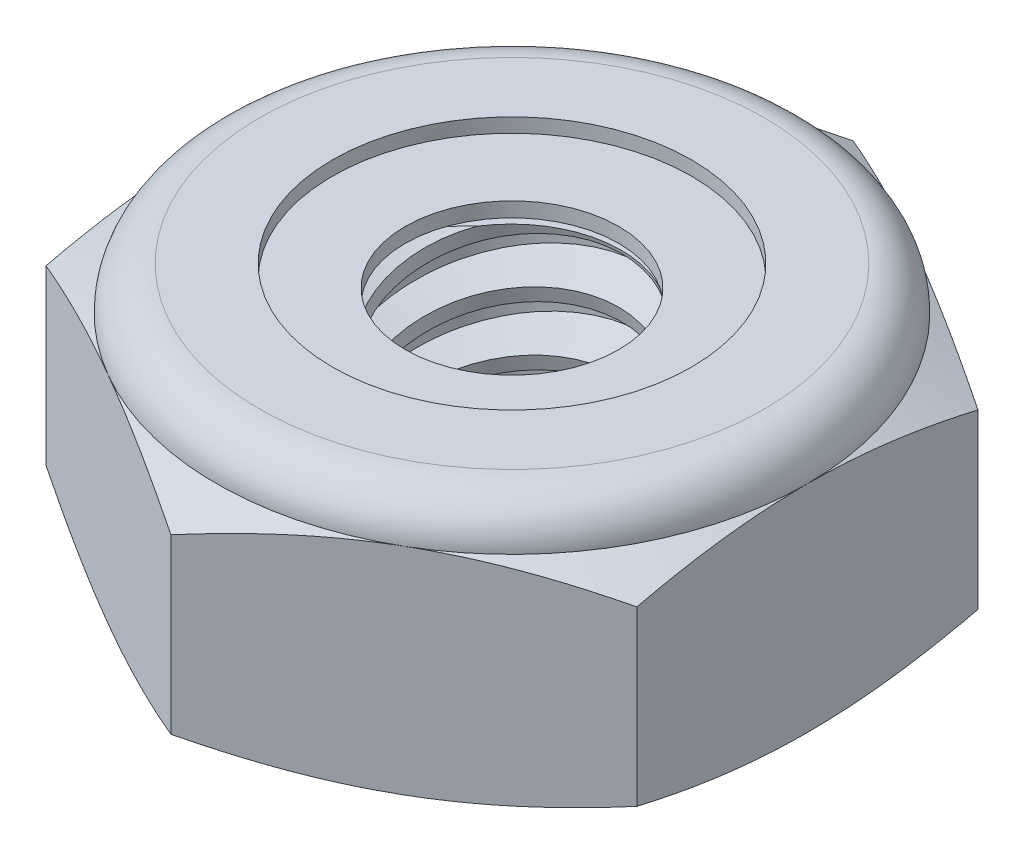
SolidWorks part; units mm, degrees
ref_plane "Front" through (0, 0, 0) normal (0, 0, 1) x (1, 0, 0)
ref_plane "Top" through (0, 0, 0) normal (0, 1, 0) x (1, 0, 0)
ref_plane "Right" through (0, 0, 0) normal (1, 0, 0) x (0, 0, -1)
sketch "Sketch1" plane through (0, 0, 0) normal (0, 1, 0) x (1, 0, 0)
  line L1 (0, 3.6662) -> (-3.175, 1.8331)
  line L2 (-3.175, 1.8331) -> (-3.175, -1.8331)
  line L3 (-3.175, -1.8331) -> (0, -3.6662)
  line L4 (0, -3.6662) -> (3.175, -1.8331)
  line L5 (3.175, -1.8331) -> (3.175, 1.8331)
  line L6 (3.175, 1.8331) -> (0, 3.6662)
  circle A0 centre (0, 0) radius 3.175 construction
  dimension "Hex Flats" = 6.35
extrude "Extrude1" add sketch "Sketch1" along normal blind 2.7781
sketch "Sketch2" plane through (0, 0, 0) normal (1, 0, 0) x (0, 0, -1)
  line L0 (-1.4224, 0) -> (-1.4224, 2.7781) construction
  line L1 (0, 0) -> (1.4224, 0)
  line L2 (0, 0) -> (0, 2.7781)
  line L3 (0, 2.7781) -> (1.4224, 2.7781)
  line L4 (1.4224, 0) -> (1.4224, 2.7781)
  line L5 (-1.8331, 2.7781) -> (1.8331, 2.7781) construction
  line L7 (0, -1.4224) -> (0, 0) construction
  dimension "Thread Dia" = 2.8448
revolve "Revolve1" add sketch "Sketch2" angle 360 about L7
sketch "Sketch3" plane through (0, 0, 0) normal (1, 0, 0) x (0, 0, -1)
  line L0 (1.4224, 2.7781) -> (-1.4224, 2.7781) construction
  line L1 (-1.4224, 2.7781) -> (-1.4224, 2.1431) construction
  line L2 (-1.4224, 2.1431) -> (1.4224, 2.7781) construction
  line L3 (1.4224, 2.7781) -> (1.4397, 2.7007) construction
  line L4 (1.4397, 2.7007) -> (1.5607, 2.1584)
  line L5 (1.5607, 2.1584) -> (1.1821, 2.2772)
  line L6 (1.1821, 2.2772) -> (1.1475, 2.4321)
  line L7 (1.1475, 2.4321) -> (1.4397, 2.7007)
  line L8 (1.1648, 2.3546) -> (1.5002, 2.4295) construction
  line L9 (1.4224, 2.7781) -> (1.4224, 2.4121) construction
  line L10 (1.4224, 2.4121) -> (-1.4224, 1.7771) construction
  line L11 (-1.4224, 1.7771) -> (-1.4224, 2.1431) construction
  line L12 (-0.1526, 2.7781) -> (0.1526, 1.4112) construction
  line L13 (-1.4224, 0) -> (-1.4224, 2.7781) construction
  line L14 (0, 2.7781) -> (1.4224, 2.7781) construction
  line L15 (1.4224, 0) -> (1.4224, 2.7781) construction
  point P13 (0, 2.0946)
  dimension "D1" = 0.0794
  dimension "D2" = 0.1588
  dimension "Thread Pitch" = 0.635
  dimension "D4" = 60
  dimension "D5" = 0.635
revolve "Cut-Revolve1" cut sketch "Sketch3" angle 360 about L12
pattern_linear "LPattern1" count 4 spacing 0.635 along (0, -1, 0) count 2 spacing 0.635 along (0, 1, 0) of "Cut-Revolve1"
sketch "Sketch4" plane through (0, 0, 0) normal (1, 0, 0) x (0, 0, -1)
  line L0 (0, 2.7781) -> (1.4224, 2.7781)
  line L1 (1.4224, 2.7781) -> (1.1475, 2.6499)
  line L2 (1.1475, 2.6499) -> (1.1475, 0.1282)
  line L3 (1.1475, 0.1282) -> (1.4224, 0)
  line L4 (1.4224, 0) -> (0, 0)
  line L5 (0, 0) -> (0, 2.7781)
  line L6 (1.4224, 0) -> (1.4224, 2.7781) construction
  line L7 (0, 2.7781) -> (1.4224, 2.7781) construction
  line L8 (0, 0) -> (1.4224, 0) construction
  line L9 (0, 0) -> (0, 2.7781) construction
  line L10 (0, 2.7781) -> (0, 3.0815) construction
  dimension "D1" = 25
revolve "Cut-Revolve2" cut sketch "Sketch4" angle 360 about L10
combine bodies "Combine1" operation type subtract main body 112 bodies to subtract 111
sketch "Sketch5" plane through (0, 0, 0) normal (1, 0, 0) x (0, 0, -1)
  line L0 (0, 0) -> (3.175, 0)
  line L1 (3.175, 0) -> (3.6662, 0.229)
  line L2 (3.6662, 0.229) -> (3.6662, 2.0861)
  line L3 (3.6662, 2.0861) -> (3.175, 2.3151)
  line L4 (2.712, 2.7781) -> (2.712, 4.0481)
  line L5 (2.712, 4.0481) -> (4.9362, 4.0481)
  line L6 (4.9362, 4.0481) -> (4.9362, -1.27)
  line L7 (4.9362, -1.27) -> (0, -1.27)
  line L8 (0, -1.27) -> (0, 0)
  line L9 (3.175, 2.3151) -> (3.175, 0) construction
  line L10 (0, 0) -> (1.4224, 0) construction
  line L13 (3.6662, 1.1576) -> (4.9362, 1.1576) construction
  line L14 (3.6662, 2.7781) -> (3.6662, 0) construction
  line L15 (0, 0) -> (0, 4.0481) construction
  line L20 (0, 4.0481) -> (2.712, 4.0481) construction
  line L22 (0, 2.7781) -> (1.4224, 2.7781) construction
  arc A0 (3.175, 2.3151) -> (2.712, 2.7781) centre (2.712, 2.3151) ccw
  dimension "D1" = 25
  dimension "D2" = 1.27
  dimension "D3" = 2.7781
  dimension "D4" = 0.463
revolve "Cut-Revolve3" cut sketch "Sketch5" angle 360 about L15
sketch "Sketch6" plane through (0, 0, 0) normal (1, 0, 0) x (0, 0, -1)
  line L0 (0, 2.3151) -> (3.0226, 2.3151)
  line L1 (2.712, 2.6257) -> (1.9297, 2.6257)
  line L2 (0, 4.0481) -> (0, 2.3151)
  line L3 (1.9297, 4.0481) -> (0, 4.0481)
  line L4 (0, 4.0481) -> (2.712, 4.0481) construction
  line L5 (0, 0) -> (0, 4.0481) construction
  line L6 (0, 4.0481) -> (0, 44.323) construction
  line L7 (1.9297, 2.6257) -> (1.9297, 4.0481)
  line L8 (2.712, 2.7781) -> (2.712, 2.6257) construction
  line L9 (1.9297, 2.6257) -> (1.1475, 2.6257) construction
  line L10 (1.1475, 2.6257) -> (1.1475, 2.6499) construction
  arc A0 (3.0226, 2.3151) -> (2.712, 2.6257) centre (2.712, 2.3151) ccw
  arc A1 (3.175, 2.3151) -> (2.712, 2.7781) centre (2.712, 2.3151) ccw construction
  dimension "D1" = 0.1524
revolve "Cut-Revolve4" cut sketch "Sketch6" angle 360 about L6
sketch "Sketch7" plane through (0, 0, 0) normal (1, 0, 0) x (0, 0, -1)
  line L0 (1.1475, 2.3913) -> (2.9337, 2.3913)
  line L1 (2.712, 2.5495) -> (1.1475, 2.5495)
  line L2 (1.1475, 2.5495) -> (1.1475, 2.3913)
  line L3 (1.1475, 2.3913) -> (0, 2.3913) construction
  line L4 (0, 2.3913) -> (0, 2.5495) construction
  line L5 (0, 2.5495) -> (1.1475, 2.5495) construction
  line L6 (1.1475, 2.3913) -> (1.1475, 2.3151) construction
  line L7 (0, 2.3151) -> (3.0226, 2.3151) construction
  line L8 (2.712, 2.5495) -> (2.712, 2.6257) construction
  arc A0 (2.9337, 2.3913) -> (2.712, 2.5495) centre (2.712, 2.3151) ccw
  arc A2 (3.0226, 2.3151) -> (2.712, 2.6257) centre (2.712, 2.3151) ccw construction
  dimension "D1" = 0.0762
revolve "Revolve2" add sketch "Sketch7" angle 360 about L4
equation "\"D1@Sketch3\"=\"Thread Pitch@Sketch3\"/8"
equation "\"D2@Sketch3\"=\"Thread Pitch@Sketch3\"/4"
equation "\"D5@Sketch3\"=\"Thread Pitch@Sketch3\""
equation "\"D4@LPattern1\"=\"Thread Pitch@Sketch3\""
equation "\"D3@LPattern1\"=\"Thread Pitch@Sketch3\""
equation "\"D1@LPattern1\"=\"Height@Extrude1\"/\"Thread Pitch@Sketch3\""
equation "\"D4@Sketch5\"=\"Height@Extrude1\"/6"
